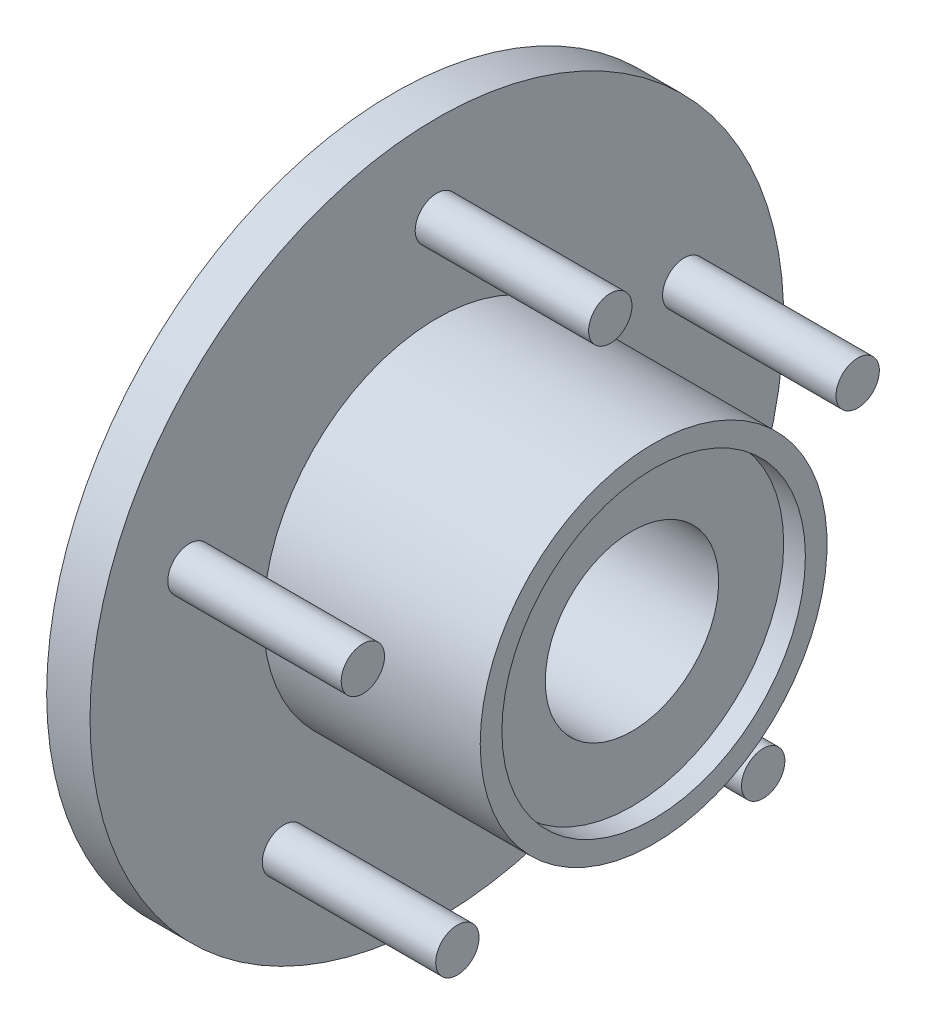
SolidWorks part; units mm, degrees
ref_plane "Front Plane" through (0, 0, 0) normal (0, 0, 1) x (1, 0, 0)
ref_plane "Top Plane" through (0, 0, 0) normal (0, 1, 0) x (1, 0, 0)
ref_plane "Right Plane" through (0, 0, 0) normal (1, 0, 0) x (0, 0, -1)
sketch "Sketch1" plane through (0, 0, 0) normal (0, 0, 1) x (1, 0, 0)
  line L0 (0, 25.4) -> (12.7, 25.4)
  line L1 (0, -55) -> (0, 55) construction
  line L2 (12.7, 25.4) -> (12.7, 50.8)
  line L3 (12.7, 50.8) -> (19.05, 50.8)
  line L4 (19.05, 50.8) -> (19.05, 25.4)
  line L5 (19.05, 25.4) -> (50.8, 25.4)
  line L6 (50.8, 25.4) -> (50.8, 22.225)
  line L7 (50.8, 22.225) -> (47.625, 22.225)
  line L8 (47.625, 22.225) -> (47.625, 12.7)
  line L9 (3.175, 12.7) -> (47.625, 12.7)
  line L10 (55, 0) -> (-55, 0) construction
  line L11 (0, 0) -> (85.204, 0) construction
  line L12 (0, 25.4) -> (0, 22.225)
  line L13 (0, 22.225) -> (3.175, 22.225)
  line L14 (3.175, 22.225) -> (3.175, 12.7)
  dimension "D1" = 6.35
  dimension "D2" = 12.7
  dimension "D3" = 50.8
  dimension "D4" = 3.175
  dimension "D5" = 12.7
  dimension "D6" = 3.175
  dimension "D7" = 25.4
  dimension "D8" = 50.8
  dimension "D9" = 3.175
  dimension "D10" = 3.175
revolve "Revolve1" add sketch "Sketch1" angle 360 about L11
sketch "Sketch3" plane through (19.05, 0, 0) normal (1, 0, 0) x (0, 0, -1)
  line L0 (0, 27.94) -> (0, -27.94) construction
  line L1 (0, 25.4) -> (0, 50.8) construction
  line L2 (27.94, 0) -> (-27.94, 0) construction
  circle A0 centre (0, 38.1) radius 3.175
  circle A1 centre (0, 0) radius 25.4 construction
  circle A2 centre (0, 0) radius 50.8 construction
  dimension "D1" = 6.35
  dimension "D2" = 38.1
extrude "Boss-Extrude1" add sketch "Sketch3" along normal blind 25.4
ref_axis "Axis1" through (53.34, 0, 0) along (-1, 0, 0)
pattern_circular "CirPattern3" count 5 over 360 about axis through (53.34, 0, 0) along (-1, 0, 0) of "Boss-Extrude1"
